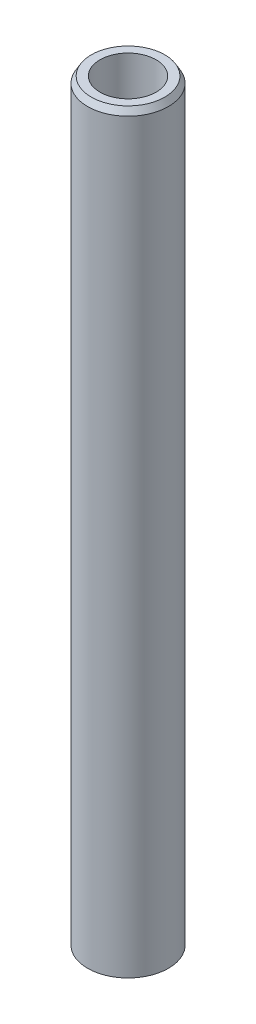
SolidWorks part; units mm, degrees
ref_plane "Front Plane" through (0, 0, 0) normal (0, 0, 1) x (1, 0, 0)
ref_plane "Top Plane" through (0, 0, 0) normal (0, 1, 0) x (1, 0, 0)
ref_plane "Right Plane" through (0, 0, 0) normal (1, 0, 0) x (0, 0, -1)
sketch "Sketch1" plane through (0, 0, 0) normal (0, 1, 0) x (1, 0, 0)
  circle A0 centre (0, 0) radius 10
  dimension "SHAFT_OD" = 20
extrude "Boss-Extrude1" add sketch "Sketch1" along normal blind 187.3233
sketch "Sketch2" plane through (0, 0, 0) normal (0, 1, 0) x (1, 0, 0)
  circle A0 centre (0, 0) radius 6.9546
  dimension "BORE_D" = 13.9092
extrude "Cut-Extrude1" cut sketch "Sketch2" along normal through all
chamfer "Chamfer1" distance 1.5709 angle 30 2 edges at (0, 187.3233, 10) (0, 0, 10) first distance on face at (0, 187.3233, 10) first distance on face at (0, 0, 6.9546)
